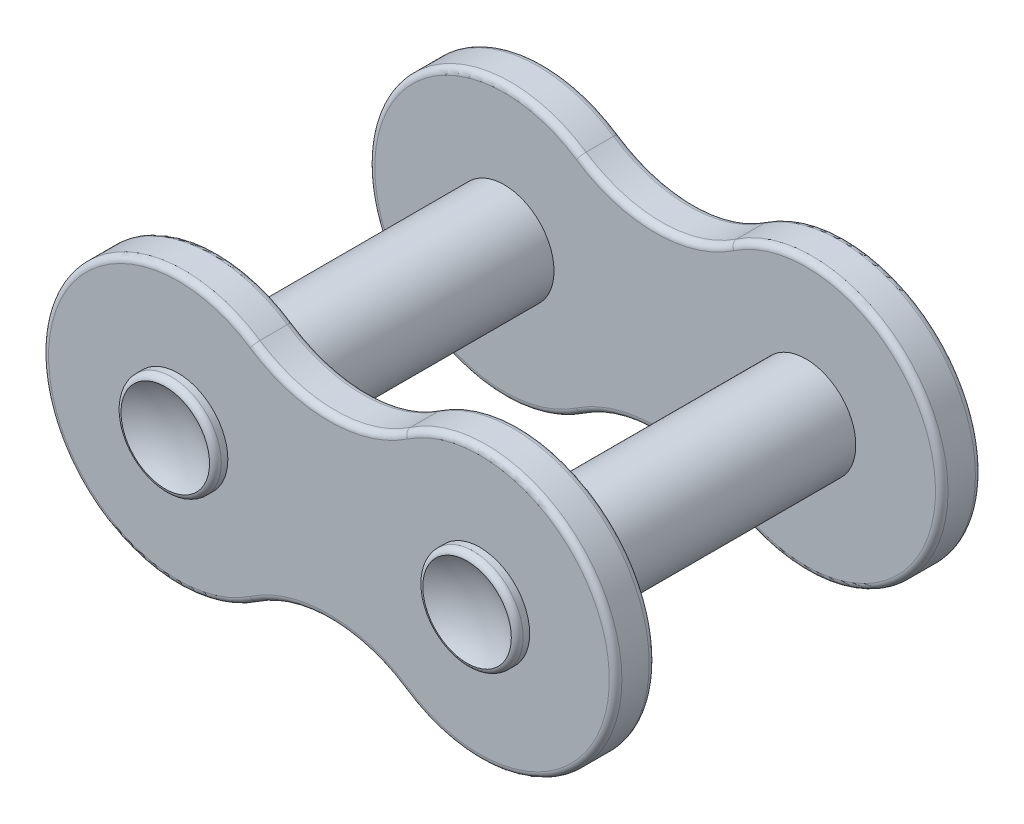
SolidWorks part; units mm, degrees
ref_plane "Front Plane" through (0, 0, 0) normal (0, 0, 1) x (1, 0, 0)
ref_plane "Top Plane" through (0, 0, 0) normal (0, 1, 0) x (1, 0, 0)
ref_plane "Right Plane" through (0, 0, 0) normal (1, 0, 0) x (0, 0, -1)
sketch "Sketch2" plane through (0, 0, 0) normal (0, 0, 1) x (1, 0, 0)
  line L0 (0, 4.9902) -> (0, 3.5714) construction
  line L1 (0, 0) -> (-6, 0) construction
  arc A0 (-2.9931, 4.4824) -> (-2.9931, -4.4824) centre (-6, 0) ccw
  circle A1 centre (-6, 0) radius 1.98
  arc A2 (2.9931, 4.4824) -> (2.9931, -4.4824) centre (6, 0) cw
  circle A3 centre (6, 0) radius 1.98
  arc A4 (-2.9931, 4.4824) -> (2.9931, 4.4824) centre (0, 8.9443) ccw
  arc A5 (-2.9931, -4.4824) -> (2.9931, -4.4824) centre (0, -8.9443) cw
  dimension "D1" = 10.795
  dimension "D2" = 3.96
  dimension "D4" = 5.3728
  dimension "D3" = 6
extrude "Boss-Extrude2" add sketch "Sketch2" along normal blind 1.5875
sketch "Sketch3" plane through (0, 0, 0) normal (0, 0, 1) x (1, 0, 0)
  circle A0 centre (-6, 0) radius 1.98 construction
  circle A1 centre (-6, 0) radius 1.98
extrude "Boss-Extrude3" add sketch "Sketch3" along normal blind 15.0652 and the other way blind 0.508
ref_plane "Plane1" through (0, 0, 7.2786) normal (0, 0, -1) x (-1, 0, 0)
mirror "Mirror1" about plane through (0, 0, 7.2786) normal (0, 0, -1) of "Boss-Extrude2"
sketch "Sketch5" plane through (0, 0, 0) normal (0, 1, 0) x (1, 0, 0)
  line L0 (-6, -14.5572) -> (-6, -21.1612) construction
  line L1 (-6, -15.3192) -> (-8.1099, -15.3192)
  line L2 (-7.98, -14.5572) -> (-4.02, -14.5572) construction
  line L3 (-6, -14.5572) -> (-6, -15.3192)
  arc A0 (-8.1099, -15.3192) -> (-6, -14.5572) centre (-6, -17.8592) cw
  point P7 (0, 0)
  point P8 (0, 0)
  dimension "D2" = 3.302
  dimension "D1" = 0.762
revolve "Cut-Revolve1" cut sketch "Sketch5" angle 360 about L0
mirror "Mirror2" about plane through (0, 0, 7.2786) normal (0, 0, -1) of "Cut-Revolve1"
mirror "Mirror3" about plane through (0, 0, 0) normal (1, 0, 0) of "Mirror2", "Boss-Extrude3"
fillet "Fillet1" radius 0.25 16 edges at (11.3975, 0, 0) (0, -3.5714, 0) (-11.3975, 0, 0) (11.3975, 0, 1.5875) (0, -3.5714, 1.5875) (-11.3975, 0, 1.5875) (11.3975, 0, 12.9697) (0, -3.5714, 12.9697) (-11.3975, 0, 12.9697) (11.3975, 0, 14.5572) (0, -3.5714, 14.5572) (-11.3975, 0, 14.5572) (0, 3.5714, 0) (0, 3.5714, 1.5875) (0, 3.5714, 12.9697) (0, 3.5714, 14.5572)
fillet "Fillet2" radius 0.25 4 edges at (-4.02, 0, -0.508) (4.02, 0, -0.508) (4.02, 0, 15.0652) (-4.02, 0, 15.0652)
